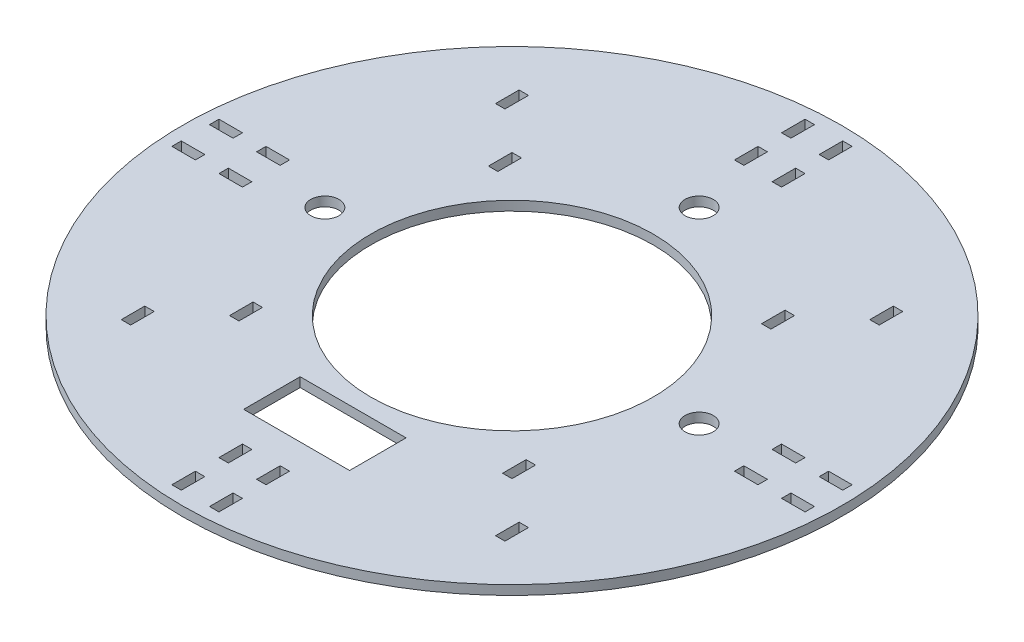
SolidWorks part; units mm, degrees
ref_plane "Front Plane" through (0, 0, 0) normal (0, 0, 1) x (1, 0, 0)
ref_plane "Top Plane" through (0, 0, 0) normal (0, 1, 0) x (1, 0, 0)
ref_plane "Right Plane" through (0, 0, 0) normal (1, 0, 0) x (0, 0, -1)
sketch "Sketch1" plane through (0, 0, 0) normal (0, 1, 0) x (1, 0, 0)
  line L0 (-49.4975, 49.4975) -> (-30, 30) construction
  line L1 (-52.2487, 5) -> (-67.2487, 5) construction
  line L2 (-67.2487, 5) -> (-67.2487, -5) construction
  line L3 (-67.2487, -5) -> (-52.2487, -5) construction
  line L4 (-52.2487, -5) -> (-52.2487, 5) construction
  line L5 (-30, -30) -> (30, 30) construction
  line L6 (-30, 30) -> (30, -30) construction
  line L7 (-30, 30) -> (-28, 30)
  line L8 (-30, 30) -> (-30, 25)
  line L9 (-30, 25) -> (-28, 25)
  line L10 (-28, 30) -> (-28, 25)
  line L11 (30, 30) -> (28, 30)
  line L12 (30, 30) -> (30, 25)
  line L13 (30, 25) -> (28, 25)
  line L14 (28, 30) -> (28, 25)
  line L15 (-30, -30) -> (-28, -30)
  line L16 (-30, -30) -> (-30, -25)
  line L17 (-30, -25) -> (-28, -25)
  line L18 (-28, -30) -> (-28, -25)
  line L19 (30, -30) -> (28, -30)
  line L20 (30, -30) -> (30, -25)
  line L21 (30, -25) -> (28, -25)
  line L22 (28, -30) -> (28, -25)
  line L23 (30, 30) -> (49.4975, 49.4975) construction
  line L24 (-49.4975, -49.4975) -> (-30, -30) construction
  line L25 (-30, -30) -> (-30, 30) construction
  line L26 (-30, 30) -> (30, 30) construction
  line L27 (30, 30) -> (30, -30) construction
  line L28 (30, -30) -> (30.057, -29.7836) construction
  line L29 (49.4975, -49.4975) -> (30, -30) construction
  line L30 (0, 49.4975) -> (0, 70) construction
  line L31 (-40.7487, 42.2487) -> (-38.7487, 42.2487)
  line L32 (-40.7487, 42.2487) -> (-40.7487, 37.2487)
  line L33 (-40.7487, 37.2487) -> (-38.7487, 37.2487)
  line L34 (-38.7487, 42.2487) -> (-38.7487, 37.2487)
  line L35 (-40.7487, 42.2487) -> (-38.7487, 37.2487) construction
  line L36 (-40.7487, 37.2487) -> (-38.7487, 42.2487) construction
  line L37 (38.7487, 42.2487) -> (40.7487, 42.2487)
  line L38 (38.7487, 42.2487) -> (38.7487, 37.2487)
  line L39 (38.7487, 37.2487) -> (40.7487, 37.2487)
  line L40 (40.7487, 42.2487) -> (40.7487, 37.2487)
  line L41 (38.7487, 42.2487) -> (40.7487, 37.2487) construction
  line L42 (38.7487, 37.2487) -> (40.7487, 42.2487) construction
  line L43 (38.7487, -37.2487) -> (40.7487, -37.2487)
  line L44 (38.7487, -37.2487) -> (38.7487, -42.2487)
  line L45 (38.7487, -42.2487) -> (40.7487, -42.2487)
  line L46 (40.7487, -37.2487) -> (40.7487, -42.2487)
  line L47 (38.7487, -37.2487) -> (40.7487, -42.2487) construction
  line L48 (38.7487, -42.2487) -> (40.7487, -37.2487) construction
  line L49 (-40.7487, -37.2487) -> (-38.7487, -37.2487)
  line L50 (-40.7487, -37.2487) -> (-40.7487, -42.2487)
  line L51 (-40.7487, -42.2487) -> (-38.7487, -42.2487)
  line L52 (-38.7487, -37.2487) -> (-38.7487, -42.2487)
  line L53 (-40.7487, -37.2487) -> (-38.7487, -42.2487) construction
  line L54 (-40.7487, -42.2487) -> (-38.7487, -37.2487) construction
  line L55 (-49.4975, 0) -> (-70, 0) construction
  line L56 (49.4975, 0) -> (70, 0) construction
  line L57 (0, -49.4975) -> (0, -70) construction
  line L58 (-49.4975, 0) -> (-30, 0) construction
  line L60 (-11.25, -33.7487) -> (11.25, -33.7487)
  line L61 (-11.25, -33.7487) -> (-11.25, -45.7487)
  line L62 (-11.25, -45.7487) -> (11.25, -45.7487)
  line L63 (-5, 52.2487) -> (5, 67.2487) construction
  line L64 (-5, 67.2487) -> (5, 52.2487) construction
  line L65 (-5, 52.2487) -> (5, 52.2487) construction
  line L66 (5, 52.2487) -> (5, 67.2487) construction
  line L67 (5, 67.2487) -> (-5, 67.2487) construction
  line L68 (-5, 67.2487) -> (-5, 52.2487) construction
  line L69 (52.2487, -5) -> (67.2487, 5) construction
  line L70 (52.2487, 5) -> (67.2487, -5) construction
  line L71 (52.2487, -5) -> (67.2487, -5) construction
  line L72 (67.2487, -5) -> (67.2487, 5) construction
  line L73 (67.2487, 5) -> (52.2487, 5) construction
  line L74 (52.2487, 5) -> (52.2487, -5) construction
  line L75 (-5, -52.2487) -> (5, -67.2487) construction
  line L76 (-5, -67.2487) -> (5, -52.2487) construction
  line L77 (-5, -52.2487) -> (5, -52.2487) construction
  line L78 (5, -52.2487) -> (5, -67.2487) construction
  line L79 (5, -67.2487) -> (-5, -67.2487) construction
  line L80 (-5, -67.2487) -> (-5, -52.2487) construction
  line L81 (-67.2487, 5) -> (-52.2487, -5) construction
  line L82 (-67.2487, -5) -> (-52.2487, 5) construction
  line L83 (-67.2487, 5) -> (-62.2487, 5)
  line L84 (-67.2487, 5) -> (-67.2487, 3)
  line L85 (-67.2487, 3) -> (-62.2487, 3)
  line L86 (-62.2487, 5) -> (-62.2487, 3)
  line L87 (-67.2487, -5) -> (-62.2487, -5)
  line L88 (-67.2487, -5) -> (-67.2487, -3)
  line L89 (-67.2487, -3) -> (-62.2487, -3)
  line L90 (-62.2487, -5) -> (-62.2487, -3)
  line L91 (-52.2487, -5) -> (-57.2487, -5)
  line L92 (-52.2487, -5) -> (-52.2487, -3)
  line L93 (-52.2487, -3) -> (-57.2487, -3)
  line L94 (-57.2487, -5) -> (-57.2487, -3)
  line L95 (-52.2487, 5) -> (-57.2487, 5)
  line L96 (-52.2487, 5) -> (-52.2487, 3)
  line L97 (-52.2487, 3) -> (-57.2487, 3)
  line L98 (-57.2487, 5) -> (-57.2487, 3)
  line L99 (-5, 67.2487) -> (-3, 67.2487)
  line L100 (-5, 67.2487) -> (-5, 62.2487)
  line L101 (-5, 62.2487) -> (-3, 62.2487)
  line L102 (-3, 67.2487) -> (-3, 62.2487)
  line L103 (-5, 52.2487) -> (-3, 52.2487)
  line L104 (-5, 52.2487) -> (-5, 57.2487)
  line L105 (-5, 57.2487) -> (-3, 57.2487)
  line L106 (-3, 52.2487) -> (-3, 57.2487)
  line L107 (5, 52.2487) -> (3, 52.2487)
  line L108 (5, 52.2487) -> (5, 57.2487)
  line L109 (5, 57.2487) -> (3, 57.2487)
  line L110 (3, 52.2487) -> (3, 57.2487)
  line L111 (5, 67.2487) -> (3, 67.2487)
  line L112 (5, 67.2487) -> (5, 62.2487)
  line L113 (5, 62.2487) -> (3, 62.2487)
  line L114 (3, 67.2487) -> (3, 62.2487)
  line L115 (52.2487, 5) -> (57.2487, 5)
  line L116 (52.2487, 5) -> (52.2487, 3)
  line L117 (52.2487, 3) -> (57.2487, 3)
  line L118 (57.2487, 5) -> (57.2487, 3)
  line L119 (52.2487, -5) -> (57.2487, -5)
  line L120 (52.2487, -5) -> (52.2487, -3)
  line L121 (52.2487, -3) -> (57.2487, -3)
  line L122 (57.2487, -5) -> (57.2487, -3)
  line L123 (67.2487, 5) -> (62.2487, 5)
  line L124 (67.2487, 5) -> (67.2487, 3)
  line L125 (67.2487, 3) -> (62.2487, 3)
  line L126 (62.2487, 5) -> (62.2487, 3)
  line L127 (67.2487, -5) -> (62.2487, -5)
  line L128 (67.2487, -5) -> (67.2487, -3)
  line L129 (67.2487, -3) -> (62.2487, -3)
  line L130 (62.2487, -5) -> (62.2487, -3)
  line L131 (-5, -52.2487) -> (-3, -52.2487)
  line L132 (-5, -52.2487) -> (-5, -57.2487)
  line L133 (-5, -57.2487) -> (-3, -57.2487)
  line L134 (-3, -52.2487) -> (-3, -57.2487)
  line L135 (5, -52.2487) -> (3, -52.2487)
  line L136 (5, -52.2487) -> (5, -57.2487)
  line L137 (5, -57.2487) -> (3, -57.2487)
  line L138 (3, -52.2487) -> (3, -57.2487)
  line L139 (5, -67.2487) -> (3, -67.2487)
  line L140 (5, -67.2487) -> (5, -62.2487)
  line L141 (5, -62.2487) -> (3, -62.2487)
  line L142 (3, -67.2487) -> (3, -62.2487)
  line L143 (-5, -67.2487) -> (-3, -67.2487)
  line L144 (-5, -67.2487) -> (-5, -62.2487)
  line L145 (-5, -62.2487) -> (-3, -62.2487)
  line L146 (-3, -67.2487) -> (-3, -62.2487)
  line L147 (0, 49.4975) -> (0, 30) construction
  line L148 (30, 0) -> (49.4975, 0) construction
  line L149 (0, -30) -> (0, -49.4975) construction
  line L150 (-49.4975, -49.4975) -> (-49.4975, 49.4975) construction
  line L151 (-49.4975, 49.4975) -> (49.4975, 49.4975) construction
  line L152 (49.4975, 49.4975) -> (49.4975, -49.4975) construction
  line L153 (49.4975, -49.4975) -> (-49.4975, -49.4975) construction
  line L154 (-30, -30) -> (30, -30) construction
  line L155 (-52.2487, 5) -> (-67.2487, 5) construction
  line L156 (11.25, -33.7487) -> (11.25, -45.7487)
  line L157 (-11.25, -33.7487) -> (11.25, -45.7487) construction
  line L158 (-11.25, -45.7487) -> (11.25, -33.7487) construction
  circle A0 centre (0, 0) radius 30
  circle A1 centre (0, 0) radius 70
  circle A2 centre (0, -39.7487) radius 3
  circle A3 centre (39.7487, 0) radius 3
  circle A4 centre (-39.7487, 0) radius 3
  circle A5 centre (0, 39.7487) radius 3
  point P20 (-39.7487, 39.7487)
  point P29 (39.7487, 39.7487)
  point P34 (39.7487, -39.7487)
  point P39 (-39.7487, -39.7487)
  point P52 (0, 59.7487)
  point P57 (59.7487, 0)
  point P62 (0, -59.7487)
  point P67 (-59.7487, 0)
  dimension "D1" = 60
  dimension "D2" = 140
  dimension "D65" = 6
  dimension "D66" = 6
  dimension "D67" = 6
  dimension "D68" = 6
  dimension "D3" = 60
  dimension "D4" = 60
  dimension "D5" = 5
  dimension "D6" = 2
  dimension "D7" = 5
  dimension "D8" = 2
  dimension "D9" = 2
  dimension "D10" = 5
  dimension "D11" = 2
  dimension "D12" = 5
  dimension "D13" = 5
  dimension "D14" = 2
  dimension "D15" = 5
  dimension "D16" = 2
  dimension "D17" = 2
  dimension "D18" = 5
  dimension "D19" = 2
  dimension "D20" = 5
  dimension "D21" = 20.5025
  dimension "D22" = 15
  dimension "D23" = 10
  dimension "D24" = 20.5025
  dimension "D25" = 15
  dimension "D26" = 10
  dimension "D27" = 20.5025
  dimension "D28" = 15
  dimension "D29" = 10
  dimension "D30" = 20.5025
  dimension "D31" = 15
  dimension "D32" = 10
  dimension "D33" = 5
  dimension "D34" = 2
  dimension "D35" = 5
  dimension "D36" = 2
  dimension "D37" = 5
  dimension "D38" = 2
  dimension "D39" = 5
  dimension "D40" = 5
  dimension "D41" = 5
  dimension "D42" = 5
  dimension "D43" = 5
  dimension "D44" = 2
  dimension "D45" = 2
  dimension "D46" = 2
  dimension "D47" = 2
  dimension "D48" = 5
  dimension "D49" = 5
  dimension "D50" = 5
  dimension "D51" = 5
  dimension "D52" = 2
  dimension "D53" = 2
  dimension "D54" = 2
  dimension "D55" = 2
  dimension "D56" = 2
  dimension "D57" = 5
  dimension "D58" = 5
  dimension "D59" = 2
  dimension "D60" = 2
  dimension "D61" = 2
  dimension "D62" = 5
  dimension "D63" = 5
  dimension "D64" = 2
  dimension "D69" = 19.4975
  dimension "D70" = 22.5
  dimension "D71" = 12
extrude "Yükseklik-Ekstrüzyon1" add sketch "Sketch1" along normal blind 2 contours A1 A5 A4 A3 L60 L156 L62 L61 L146 L143 L144 L145 L131 L134 L133 L132 L115 L118 L117 L116 L114 L111 L112 L113 L99 L102 L101 L100 L98 L95 L96 L97 L83 L86 L85 L84 L43 L46 L45 region at (-68.0201, 0, 0)
